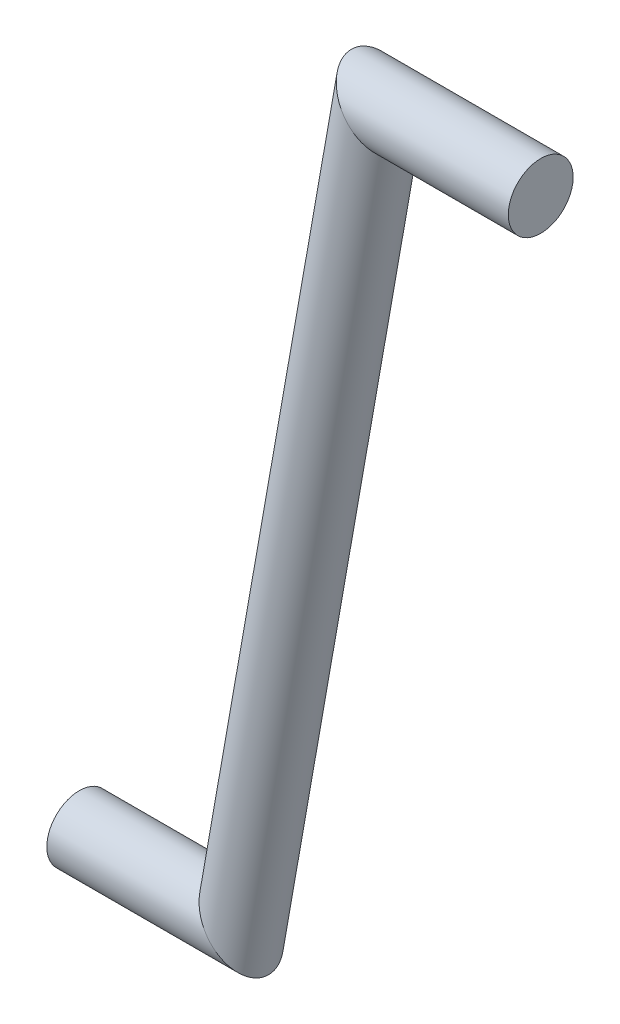
SolidWorks part; units mm, degrees
ref_plane "Front" through (0, 0, 0) normal (0, 0, 1) x (1, 0, 0)
ref_plane "Top" through (0, 0, 0) normal (0, 1, 0) x (1, 0, 0)
ref_plane "Right" through (0, 0, 0) normal (1, 0, 0) x (0, 0, -1)
sketch "Sketch4" plane through (0, 0, 0) normal (1, 0, 0) x (0, 0, -1)
  circle A0 centre (0, 0) radius 6.35
  dimension "D1" = 12.7
sketch "Sketch5" plane through (0, 0, 0) normal (0, 0, 1) x (1, 0, 0)
  line L0 (0, 0) -> (31.75, 0)
  line L1 (31.75, 0) -> (58.6222, 152.4)
  line L2 (58.6222, 152.4) -> (90.3722, 152.4)
  dimension "D1" = 31.75
  dimension "D2" = 152.4
  dimension "D3" = 31.75
  dimension "D4" = 100
sweep "Sweep3" add profiles "Sketch4" path "Sketch5"
